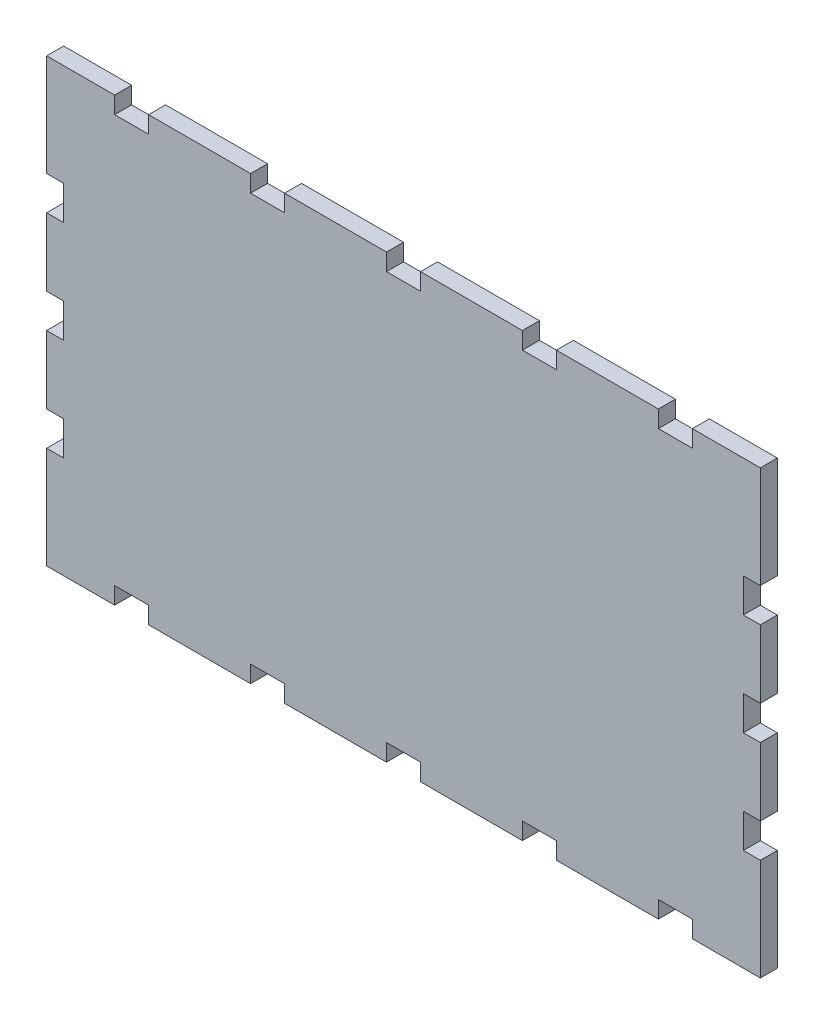
SolidWorks part; units mm, degrees
ref_plane "Ön Düzlem" through (0, 0, 0) normal (0, 0, 1) x (1, 0, 0)
ref_plane "Üst Düzlem" through (0, 0, 0) normal (0, 1, 0) x (1, 0, 0)
ref_plane "Sağ Düzlem" through (0, 0, 0) normal (1, 0, 0) x (0, 0, -1)
sketch "Sketch1" plane through (0, 0, 0) normal (0, 0, 1) x (1, 0, 0)
  line L0 (-85, 65) -> (-85, 60)
  line L1 (-105, -65) -> (-85, -65)
  line L2 (-105, -65) -> (-105, -35)
  line L3 (-105, 65) -> (-85, 65)
  line L4 (105, -65) -> (105, -35)
  line L5 (-105, -65) -> (105, 65) construction
  line L6 (-105, 65) -> (105, -65) construction
  line L7 (-85, 60) -> (-75, 60)
  line L8 (-75, 60) -> (-75, 65)
  line L10 (-5, 65) -> (-5, -55) construction
  line L11 (-85, -65) -> (-85, -60)
  line L12 (-85, -60) -> (-75, -60)
  line L13 (-75, -60) -> (-75, -65)
  line L14 (-45, 65) -> (-45, 60)
  line L15 (-35, 60) -> (-35, 65)
  line L16 (-45, 60) -> (-35, 60)
  line L17 (-45, -60) -> (-35, -60)
  line L18 (-45, -65) -> (-45, -60)
  line L19 (-35, -60) -> (-35, -65)
  line L20 (-5, 65) -> (-5, 60)
  line L21 (5, 60) -> (5, 65)
  line L22 (-5, 60) -> (5, 60)
  line L23 (-5, -60) -> (5, -60)
  line L24 (-5, -65) -> (-5, -60)
  line L25 (5, -60) -> (5, -65)
  line L26 (35, 65) -> (35, 60)
  line L27 (45, 60) -> (45, 65)
  line L28 (35, 60) -> (45, 60)
  line L29 (35, -60) -> (45, -60)
  line L30 (35, -65) -> (35, -60)
  line L31 (45, -60) -> (45, -65)
  line L32 (75, 65) -> (75, 60)
  line L33 (85, 60) -> (85, 65)
  line L34 (75, 60) -> (85, 60)
  line L35 (75, -60) -> (85, -60)
  line L36 (75, -65) -> (75, -60)
  line L37 (85, -60) -> (85, -65)
  line L38 (-75, -65) -> (-45, -65)
  line L39 (-35, -65) -> (-5, -65)
  line L40 (5, -65) -> (35, -65)
  line L41 (45, -65) -> (75, -65)
  line L42 (85, -65) -> (105, -65)
  line L43 (85, 65) -> (105, 65)
  line L44 (115, -60) -> (125, -60) [skipped]
  line L45 (115, -65) -> (115, -60) [skipped]
  line L46 (125, -60) -> (125, -65) [skipped]
  line L47 (115, 65) -> (115, 60) [skipped]
  line L48 (125, 60) -> (125, 65) [skipped]
  line L49 (115, 60) -> (125, 60) [skipped]
  line L50 (45, 65) -> (75, 65)
  line L51 (5, 65) -> (35, 65)
  line L52 (-35, 65) -> (-5, 65)
  line L53 (-75, 65) -> (-45, 65)
  line L54 (-105, 35) -> (-100, 35)
  line L55 (-100, 35) -> (-100, 25)
  line L56 (-100, 25) -> (-105, 25)
  line L57 (100, 25) -> (105, 25)
  line L58 (100, 35) -> (100, 25)
  line L59 (105, 35) -> (100, 35)
  line L60 (-105, 5) -> (-100, 5)
  line L61 (-100, 5) -> (-100, -5)
  line L62 (-100, -5) -> (-105, -5)
  line L63 (105, 5) -> (100, 5)
  line L64 (100, 5) -> (100, -5)
  line L65 (100, -5) -> (105, -5)
  line L66 (-105, -25) -> (-100, -25)
  line L67 (-100, -25) -> (-100, -35)
  line L68 (-100, -35) -> (-105, -35)
  line L69 (105, -25) -> (100, -25)
  line L70 (100, -25) -> (100, -35)
  line L71 (100, -35) -> (105, -35)
  line L72 (-105, 35) -> (-105, 65)
  line L73 (-105, 5) -> (-105, 25)
  line L74 (-105, -25) -> (-105, -5)
  line L75 (105, -25) -> (105, -5)
  line L76 (105, 5) -> (105, 25)
  line L77 (105, 35) -> (105, 65)
  point P0 (0, 0)
  point P57 (0, 0)
  point P58 (0, 0)
  point P73 (95, 35.5877)
  dimension "D1" = 210
  dimension "D2" = 130
  dimension "D3" = 20
  dimension "D4" = 5
  dimension "D5" = 10
  dimension "D7" = 30
  dimension "D8" = 5
  dimension "D9" = 10
  dimension "D10" = 30
  dimension "D12" = 5
  dimension "D13" = 30
  dimension "D14" = 20
  dimension "D15" = 20
  dimension "D6" = 6
  dimension "D11" = 3
extrude "Boss-Extrude1" add sketch "Sketch1" along normal blind 5
